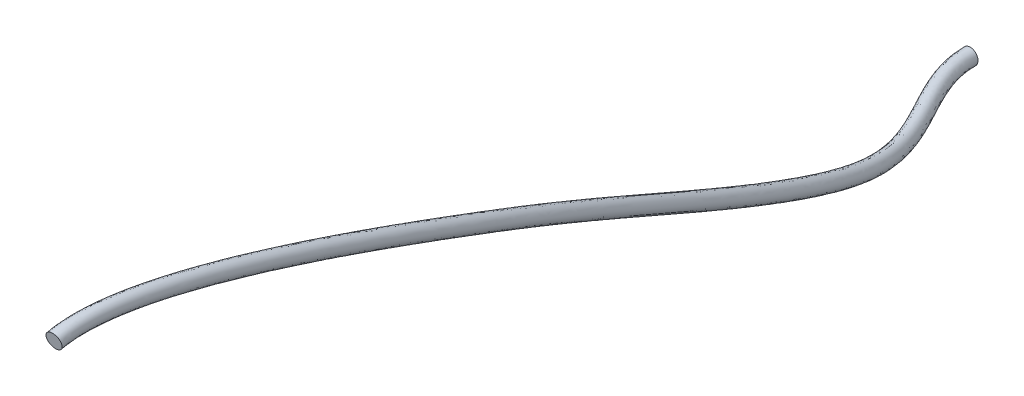
SolidWorks part; units mm, degrees
ref_plane "Front" through (0, 0, 0) normal (0, 0, 1) x (1, 0, 0)
ref_plane "Top" through (0, 0, 0) normal (0, 1, 0) x (1, 0, 0)
ref_plane "Right" through (0, 0, 0) normal (1, 0, 0) x (0, 0, -1)
sketch "Sketch1" plane through (0, 0, 0) normal (0, 0, 1) x (1, 0, 0)
  line L0 (0, 1.15) -> (0, -1.15) construction
  line L2 (1.15, 0) -> (0, 0) construction
  circle A0 centre (0, 0) radius 1.15
  dimension "D1" = 2.3
sketch3d "3DSketch1"
  line L0 (0, 0, 0) -> (0, 0, 4.778) construction
  spline S0 degree 3 poles (0, 0, 0) (0, 0, 7.8941) (10.5405, -4.1165, 14.4476) (6.2471, 13.5112, 58.9113) (4.5294, 22.9999, 85.6566) (-1.0578, 32.557, 123.1477) (-0.8869, 30.1779, 133.7729) knots 0 0 0 0 0.24207 0.43302 0.591544 1 1 1 1
sweep "Sweep1" add profiles "Sketch1" path "3DSketch1"
